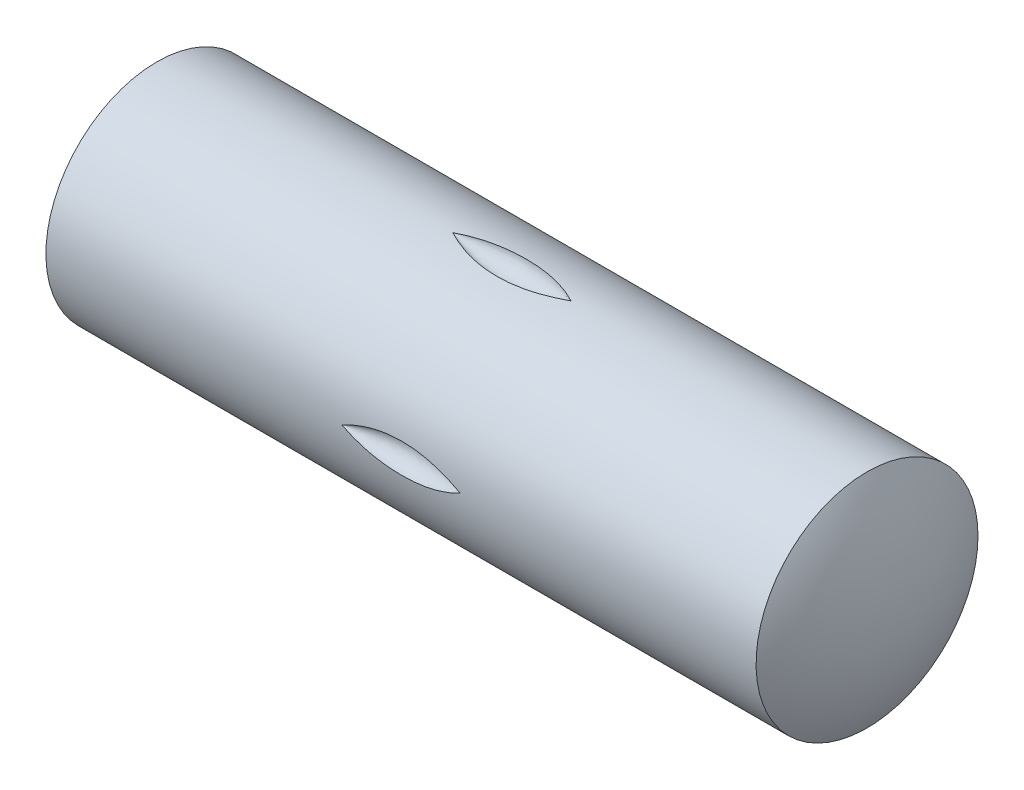
SolidWorks part; units mm, degrees
ref_plane "Plan1" through (0, 0, 0) normal (0, 0, 1) x (1, 0, 0)
ref_plane "Plan2" through (0, 0, 0) normal (0, 1, 0) x (1, 0, 0)
ref_plane "Plan3" through (0, 0, 0) normal (1, 0, 0) x (0, 0, -1)
sketch "Esquisse1" plane through (0, 0, 0) normal (0, 0, 1) x (1, 0, 0)
  line L0 (0, 0) -> (-12, 0) construction
  line L2 (-8, 2.5) -> (8, 2.5)
  line L3 (-8.67, 0) -> (8.67, 0)
  arc A0 (8, 2.5) -> (8.67, 0) centre (3.6708, 0) cw
  arc A1 (-8, 2.5) -> (-8.67, 0) centre (-3.6708, 0) ccw
  point P9 (0, 2.5)
  dimension "D1" = 8
  dimension "D2" = 2.5
  dimension "D3" = 0.67
revolve "Base-Révolution" add sketch "Esquisse1" angle 360 about L0
ref_axis "Axe1" through (50, 0, 0) along (-1, 0, 0)
ref_plane "Plan4" through (0, 2.5, 0) normal (0, 1, 0) x (-1, 0, 0)
sketch "Esquisse2" plane through (0, 2.5, 0) normal (0, 1, 0) x (-1, 0, 0)
  line L0 (0, 0) -> (-8.67, 0) construction
  line L1 (12, 0) -> (0, 0) construction
  line L2 (0, 0) -> (0, 0.335) construction
  line L3 (1.3333, 0) -> (-1.3333, 0)
  arc A0 (-8, 2.5) -> (-8, -2.5) centre (-3.6708, 0) ccw construction
  arc A1 (1.3333, 0) -> (0, 0.335) centre (0, -2.4859) ccw
  arc A2 (-1.3333, 0) -> (0, 0.335) centre (0, -2.4859) cw
  dimension "D1" = 2.6667
  dimension "D2" = 0.335
revolve "Enlever de la matière-Révolution1" cut sketch "Esquisse2" angle 360 about L0
pattern_circular "Répétition circulaire1" count 4 every 90 about axis through (50, 0, 0) along (-1, 0, 0) of "Enlever de la matière-Révolution1"
equation "\"D1@Esquisse2\"=\"D1@Esquisse1\"/3"
equation "\"D2@Esquisse2\"=\"D3@Esquisse1\"/2"
equation "\"D1@Plan4\"=\"D2@Esquisse1\""
